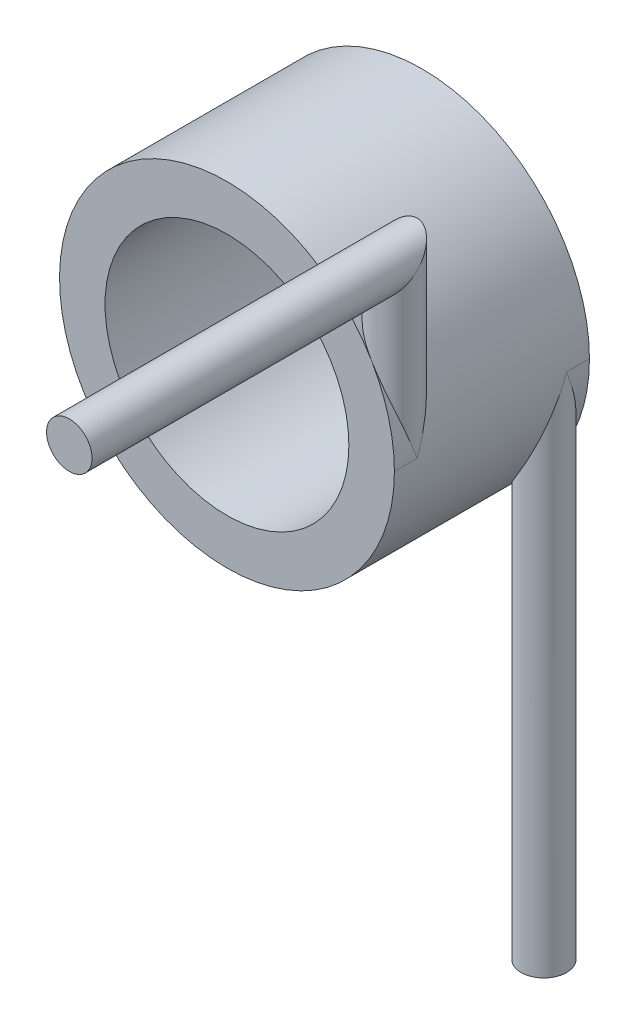
SolidWorks part; units mm, degrees
ref_plane "Front Plane" through (0, 0, 0) normal (0, 0, 1) x (1, 0, 0)
ref_plane "Top Plane" through (0, 0, 0) normal (0, 1, 0) x (1, 0, 0)
ref_plane "Right Plane" through (0, 0, 0) normal (1, 0, 0) x (0, 0, -1)
sketch "Sketch1" plane through (0, 0, 0) normal (0, 0, 1) x (1, 0, 0)
  circle A0 centre (0, 0) radius 4.7625
  circle A1 centre (0, 0) radius 6.5405
  dimension "D1" = 9.525
  dimension "D2" = 1.778
extrude "Boss-Extrude1" add sketch "Sketch1" along normal blind 7.62
sketch "Sketch2" plane through (0, 0, 0) normal (0, 1, 0) x (1, 0, 0)
  line L0 (6.5405, -7.62) -> (6.5405, 0) construction
  line L1 (6.5405, 0) -> (-6.5405, 0) construction
  line L2 (-6.5405, -7.62) -> (6.5405, -7.62) construction
  circle A0 centre (5.6515, -6.731) radius 0.889
  circle A1 centre (5.6515, -0.889) radius 0.889
  dimension "D1" = 1.778
  dimension "D2" = 0.889
  dimension "D3" = 0.889
extrude "Boss-Extrude2" add sketch "Sketch2" along normal blind 3.81 contours A0
extrude "Boss-Extrude3" add sketch "Sketch2<3>" against normal blind 20.32 contours A1
sketch "Sketch2<3>" plane through (0, 0, 0) normal (0, 1, 0) x (1, 0, 0) same geometry as "Sketch2"
sketch "Sketch4" plane through (0, -20.32, 0) normal (0, -1, 0) x (1, 0, 0)
  circle A0 centre (5.6515, 0.889) radius 0.889
ref_plane "Plane1" through (0, 0, 0.889) normal (0, 0, -1) x (-1, 0, 0)
ref_plane "Plane2" through (5.6515, 0, 0) normal (1, 0, 0) x (0, 0, -1)
sketch "Sketch6" plane through (5.6515, 0, 0) normal (1, 0, 0) x (0, 0, -1)
  line L0 (-0.889, -20.32) -> (-0.889, -23.495)
  line L1 (-0.889, -23.495) -> (-19.939, -23.495)
  dimension "D1" = 3.175
  dimension "D2" = 19.05
sweep "Sweep1" [suppressed] add profiles "Sketch4" path "Sketch6"
sketch "Sketch7" plane through (0, 3.81, 0) normal (0, 1, 0) x (1, 0, 0)
  circle A0 centre (5.6515, -6.731) radius 0.889
sketch "Sketch8" plane through (5.6515, 0, 0) normal (1, 0, 0) x (0, 0, -1)
  line L0 (-6.731, 3.81) -> (-6.731, 6.35)
  line L1 (-5.842, 3.81) -> (-7.62, 3.81) construction
  line L2 (-6.731, 6.35) -> (-19.431, 6.35)
  dimension "D1" = 2.54
  dimension "D2" = 12.7
sweep "Sweep2" add profiles "Sketch7" path "Sketch8"
